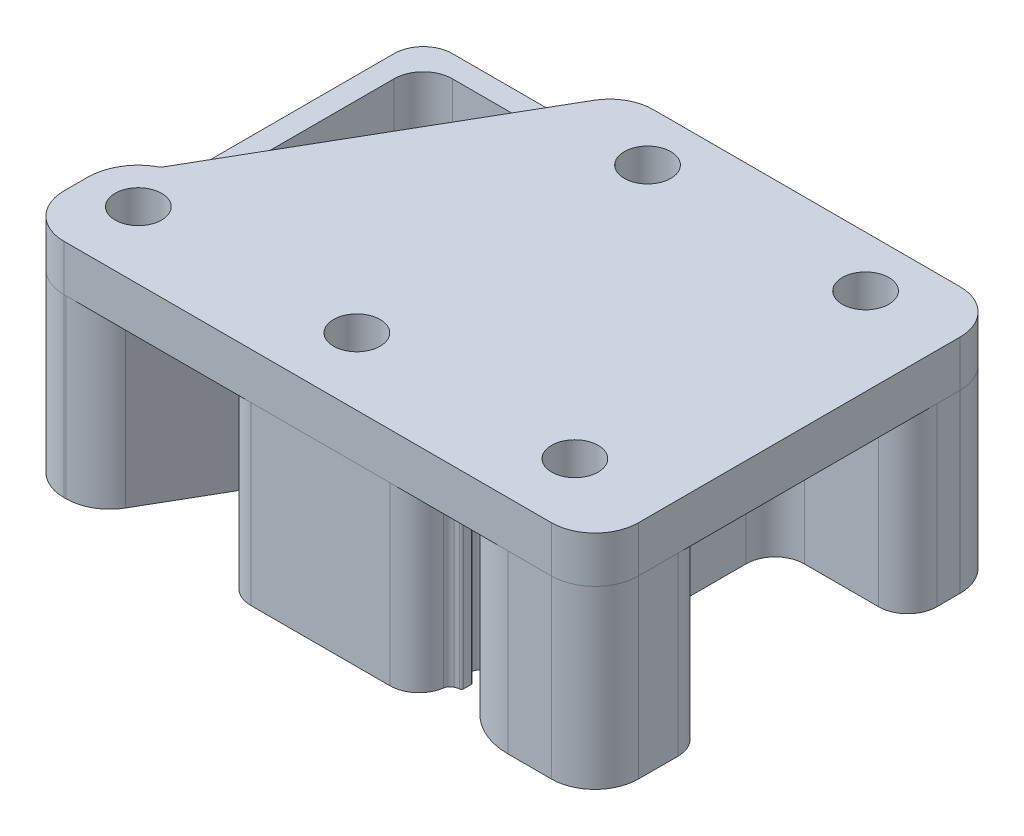
SolidWorks part; units mm, degrees
material "AISI 1045 Steel, cold drawn"
ref_plane "Front Plane" through (0, 0, 0) normal (0, 0, 1) x (1, 0, 0)
ref_plane "Top Plane" through (0, 0, 0) normal (0, 1, 0) x (1, 0, 0)
ref_plane "Right Plane" through (0, 0, 0) normal (1, 0, 0) x (0, 0, -1)
sketch "Sketch1" plane through (0, 0, 0) normal (0, 1, 0) x (1, 0, 0)
  line L0 (-13.5, -13.5) -> (-13.5, -14.619)
  line L1 (7.5, -10) -> (-7.5, -10) construction
  line L2 (7.5, -10) -> (7.5, 10) construction
  line L3 (7.5, 10) -> (-7.5, 10) construction
  line L4 (-7.5, -10) -> (-7.5, 10) construction
  line L5 (7.5, -10) -> (-7.5, 10) construction
  line L6 (7.5, 10) -> (-7.5, -10) construction
  line L7 (13.5, -13.5) -> (-13.5, -13.5) construction
  line L8 (13.5, -13.5) -> (13.5, 13.5)
  line L9 (13.5, 13.5) -> (-13.5, 13.5)
  line L10 (-13.5, -13.5) -> (-13.5, 13.5)
  line L11 (13.5, -13.5) -> (-13.5, 13.5) construction
  line L12 (13.5, 13.5) -> (-13.5, -13.5) construction
  line L13 (-13.5, -14.619) -> (13.5, -14.619)
  line L14 (13.5, -14.619) -> (13.5, -13.5)
  point P0 (0, 0)
  point P6 (0, 0)
  dimension "D1" = 15
  dimension "D2" = 27
  dimension "D3" = 1.119
  dimension "D4" = 20
extrude "Boss-Extrude1" add sketch "Sketch1" along normal mid plane 12.1
hole_wizard "M3 Clearance Hole1" positions "Sketch2" profile "Sketch3" hole size "M3" standard "ANSI Metric" end condition through all
sketch "Sketch2" plane through (0, 6.05, 0) normal (0, 1, 0) x (1, 0, 0)
  point P0 (-7.5, 10)
  point P3 (7.5, 10)
  point P6 (7.5, -10)
  point P9 (-7.5, -10)
sketch "Sketch3" plane through (-7.5, 6.05, -10) normal (1, 0, 0) x (0, 0, 1)
  line L0 (0, 0) -> (0, 12.1)
  line L1 (0, 12.1) -> (1.6, 12.1)
  line L2 (1.6, 12.1) -> (1.6, 0)
  line L5 (1.6, 0) -> (0, 0)
  line L11 (0, -6.35) -> (0, 107.95) construction
  dimension "Thru Hole Dia." = 3.2
  dimension "Thru Hole Depth" = 12.1
sketch "Sketch6" plane through (0, 6.05, 0) normal (0, 1, 0) x (1, 0, 0)
  line L0 (13.5, 13.5) -> (-13.5, 13.5) construction
  line L1 (-13.5, -14.619) -> (-28, -14.619)
  line L2 (-13.5, -14.619) -> (-13.5, 13.5)
  line L3 (-13.5, 13.5) -> (-28, 13.5)
  line L4 (-28, -14.619) -> (-28, 13.5)
  dimension "D1" = 28
extrude "Boss-Extrude3" add sketch "Sketch6" against normal up to surface (12.1 mm away) up to face at (-7.5, -6.05, -8.4)
sketch "Sketch8" plane through (0, 6.05, 0) normal (0, 1, 0) x (1, 0, 0)
  line L0 (-28, -14.619) -> (13.5, -14.619) construction
  line L2 (2.881, -10) -> (2.881, 4)
  line L3 (2.881, 4) -> (1.361, 4)
  line L4 (1.361, -14.619) -> (1.361, 4)
  line L5 (7.5, -14.619) -> (1.361, -14.619)
  arc A0 (2.881, -10) -> (7.5, -14.619) centre (7.5, -10) ccw
  dimension "D1" = 1.52
  dimension "D2" = 14
extrude "Cut-Extrude2" cut sketch "Sketch8" against normal up to surface (12.1 mm away) up to face at (-7.5, -6.05, -8.4)
sketch "Sketch9" plane through (0, 6.05, 0) normal (0, 1, 0) x (1, 0, 0)
  line L1 (2.881, 4) -> (6.306, 4)
  line L2 (2.881, 4) -> (2.881, -8)
  line L3 (2.881, -8) -> (6.306, -8)
  line L4 (6.306, 4) -> (6.306, -8)
  dimension "D1" = 3.425
  dimension "D2" = 12
extrude "Cut-Extrude3" cut sketch "Sketch9" against normal up to surface (12.1 mm away) up to face at (-7.5, -6.05, -8.4)
sketch "Sketch11" plane through (0, 6.05, 0) normal (0, 1, 0) x (1, 0, 0)
  line L1 (2.111, 0.7046) -> (2.111, 4.8734) construction
  line L4 (2.365, -998.8465) -> (2.365, 49001.1535) construction
  line L5 (2.111, 2.2598) -> (2.111, 2)
  line L6 (1.361, 3) -> (2.111, 3) construction
  line L7 (1.361, 4) -> (1.361, -14.619) construction
  line L8 (6.306, 4) -> (1.361, 4) construction
  line L9 (2.111, 2) -> (1.361, 2)
  line L10 (1.361, 2) -> (1.361, 4)
  line L11 (2.111, 4) -> (1.361, 4)
  line L12 (2.111, 3.7402) -> (2.111, 4)
  arc A2 (1.6728, 3.4989) -> (1.6728, 2.5011) centre (1.916, 3) ccw
  arc A4 (1.6728, 2.5011) -> (1.9806, 2.4085) centre (2.111, 3.4) ccw
  arc A5 (2.111, 2.2598) -> (1.9806, 2.4085) centre (1.961, 2.2598) ccw
  arc A6 (2.111, 3.7402) -> (1.9806, 3.5915) centre (1.961, 3.7402) cw
  arc A7 (1.6728, 3.4989) -> (1.9806, 3.5915) centre (2.111, 2.6) cw
  point P7 (1.361, 3)
  line M19 (1.361, -14.619) -> (1.361, 4)
  line M20 (1.361, 4) -> (6.306, 4)
  dimension "D3" = 0.555
  dimension "D4" = 1
  dimension "D5" = 1
  dimension "D6" = 0.15
  dimension "D1" = 0.254
  dimension "D2" = 0.75
  dimension "D7" = 1
extrude "Boss-Extrude4" add sketch "Sketch11" against normal up to surface (12.1 mm away) contours A2 A7 A6 L12 L10 M20 | L5 A5 A4 A2 L9 M19 region at (1.6833, 6.05, -3.7249) region at (1.6833, 6.05, -2.2751) up to face at (-7.5, -6.05, -8.4)
pattern_linear "LPattern1" count 9 spacing 2 along (0, 0, 1) of "Boss-Extrude4"
sketch "Sketch12" plane through (0, 6.05, 0) normal (0, 1, 0) x (1, 0, 0)
  circle A0 centre (2.111, 4) radius 0.5
  circle A1 centre (6.306, 4) radius 0.5
  circle A2 centre (6.306, -8) radius 0.5
  dimension "D1" = 1
extrude "Cut-Extrude5" cut sketch "Sketch12" against normal up to surface (12.1 mm away) up to face at (1.556, -6.05, 5.2005)
sketch "Sketch13" plane through (0, 6.05, 0) normal (0, 1, 0) x (1, 0, 0)
  line L3 (2.111, -14) -> (1.361, -14) construction
  line L4 (2.111, -13.7402) -> (2.111, -14) construction
  line L5 (2.111, -14) -> (1.361, -14)
  line L6 (2.111, -13.7402) -> (2.111, -14)
  line L7 (1.361, -14) -> (1.361, -13)
  arc A6 (1.6728, -12.5011) -> (1.6728, -13.4989) centre (1.916, -13) ccw construction
  arc A7 (1.6728, -13.4989) -> (1.9806, -13.5915) centre (2.111, -12.6) ccw construction
  arc A8 (2.111, -13.7402) -> (1.9806, -13.5915) centre (1.961, -13.7402) ccw construction
  arc A9 (1.361, -13) -> (1.6728, -13.4989) centre (1.916, -13) ccw
  arc A10 (1.6728, -13.4989) -> (1.9806, -13.5915) centre (2.111, -12.6) ccw
  arc A11 (2.111, -13.7402) -> (1.9806, -13.5915) centre (1.961, -13.7402) ccw
extrude "Cut-Extrude6" cut sketch "Sketch13" against normal up to surface (12.1 mm away) up to face at (1.6903, -6.05, 5.2284)
fillet "Fillet3" radius 0.5 7 edges at (5.806, 0, 8) (6.306, 0, 7.5) (5.806, 0, -4) (6.306, 0, -3.5) (2.611, 0, -4) (1.8595, 0, -3.5679) (2.881, 0, 8)
sketch "Sketch17" plane through (0, 6.05, 0) normal (0, 1, 0) x (1, 0, 0)
  line L0 (-21.1595, -14.619) -> (-15.513, -17.879)
  line L11 (-6.4019, 5.9019) -> (-3.8038, 4.4019) construction
  line L12 (-6.4019, 5.9019) -> (-2.9019, 11.9641) construction
  line L13 (-3.8038, 4.4019) -> (-0.3038, 10.4641) construction
  line L14 (-2.9019, 11.9641) -> (-0.3038, 10.4641) construction
  line L15 (-4.201, 12.7141) -> (0.9952, 9.7141) construction
  line L16 (-4.201, 12.7141) -> (-2.701, 15.3122) construction
  line L17 (0.9952, 9.7141) -> (2.4952, 12.3122) construction
  line L18 (-2.701, 15.3122) -> (2.4952, 12.3122) construction
  line L19 (-5.1029, 5.1519) -> (-0.1029, 13.8122) construction
  line L20 (-21.1595, -14.619) -> (-8.5843, 7.1619)
  line L21 (-15.513, -17.879) -> (-2.9378, 3.9019)
  line L22 (-8.5843, 7.1619) -> (-2.9378, 3.9019)
  line L23 (-22.5782, -10.8263) -> (-19.8719, -12.3888) construction
  line L24 (-22.5782, -10.8263) -> (-12.5782, 6.4942) construction
  line L25 (-19.8719, -12.3888) -> (-9.8719, 4.9317) construction
  line L26 (-12.5782, 6.4942) -> (-9.8719, 4.9317) construction
  line L27 (-28, -14.619) -> (1.361, -14.619) construction
  line L28 (-14.8719, -3.7285) -> (-17.5782, -2.166) construction
  circle A0 centre (-7.5, 10) radius 1.6 construction
  circle A1 centre (-7.5, -10) radius 1.6 construction
  dimension "D1" = 6.52
  dimension "D3" = 3
  dimension "D10" = 3
  dimension "D2" = 6
  dimension "D4" = 3
  dimension "D5" = 10
  dimension "D6" = 3.125
  dimension "D7" = 2.5
  dimension "D8" = 60
  dimension "D9" = 3
  dimension "D11" = 20
extrude "Cut-Extrude7" cut sketch "Sketch17" against normal up to surface (12.1 mm away) up to face at (1.9594, -6.05, 4.4571)
sketch "Sketch18" plane through (0, 6.05, 0) normal (0, 1, 0) x (1, 0, 0)
  line L0 (-26.0342, -14.619) -> (-26.0342, -10)
  line L2 (-14.1485, 10.3744) -> (-26.7237, -11.4065)
  line L3 (-12.344, 13.5) -> (-24.1063, -6.8729)
  line L4 (-12.344, 13.5) -> (-28, 13.5)
  line L5 (-28, 13.5) -> (-28, -14.619)
  line L7 (-28, -14.619) -> (-21.1595, -14.619) construction
  line L8 (-8.5843, 7.1619) -> (-21.1595, -14.619) construction
  line L10 (-28, -14.619) -> (-26.0342, -14.619)
  arc A2 (-24.1063, -6.8729) -> (-26.0342, -10) centre (-22.5342, -10) ccw
  point P0 (-7.5, -10)
  dimension "D2" = 3.5
  dimension "D1" = 6.425
extrude "Cut-Extrude8" cut sketch "Sketch18" against normal up to surface (12.1 mm away) contours A2 L10 | A2 L3 L4 L5 L10 region at (-22.8632, 6.05, -4.1187) up to face at (1.2277, -6.05, 4.4618)
hole_wizard "M3 Clearance Hole2" positions "Sketch19" profile "Sketch20" hole size "M3" standard "ANSI Metric" end condition up to next
sketch "Sketch19" plane through (0, 6.05, 0) normal (0, 1, 0) x (1, 0, 0)
  point P0 (-22.5342, -10)
sketch "Sketch20" plane through (-22.5342, 6.05, 10) normal (1, 0, 0) x (0, 0, 1)
  line L0 (0, 0) -> (0, 12.1)
  line L1 (0, 12.1) -> (1.6, 12.1)
  line L2 (1.6, 12.1) -> (1.6, 0)
  line L5 (1.6, 0) -> (0, 0)
  line L11 (0, -6.35) -> (0, 107.95) construction
  dimension "Thru Hole Dia." = 3.2
  dimension "Thru Hole Depth" = 12.1
fillet "Fillet4" radius 3 5 edges at (13.5, 0, 14.619) (13.5, 0, -13.5) (-12.344, 0, -13.5) (-26.0342, 0, 14.619) (-21.1595, 0, 14.619)
sketch "Sketch21" plane through (0, 6.05, 0) normal (0, 1, 0) x (1, 0, 0)
  line L0 (-8.5843, 7.1619) -> (-20.2935, -13.119) construction
  line L1 (-17.8343, -8.8595) -> (-20.8004, -7.147)
  line L2 (-17.8343, -8.8595) -> (-9.3343, 5.8629)
  line L3 (-20.8004, -7.147) -> (-12.3004, 7.5754)
  line L4 (-9.3343, 5.8629) -> (-12.3004, 7.5754)
  line L5 (-2.9378, 3.9019) -> (-8.5843, 7.1619) construction
  dimension "D3" = 17
  dimension "D1" = 3.425
  dimension "D2" = 1.5
extrude "Cut-Extrude9" cut sketch "Sketch21" against normal up to surface (12.1 mm away) up to face at (-22.5342, -6.05, 11.6)
sketch "Sketch22" plane through (0, 6.05, 0) normal (0, 1, 0) x (1, 0, 0)
  circle A0 centre (-20.8004, -7.147) radius 0.5
  circle A1 centre (-12.3004, 7.5754) radius 0.5
  circle A2 centre (-8.5843, 7.1619) radius 0.5
  circle A3 centre (-2.9378, 3.9019) radius 0.5
  arc A4 (2.544, 4.25) -> (1.6303, 3.8625) centre (2.111, 4) ccw construction
extrude "Cut-Extrude10" cut sketch "Sketch22" against normal up to surface (12.1 mm away) up to face at (-22.5342, -6.05, 11.6)
fillet "Fillet5" radius 0.5 10 edges at (-17.8343, 0, 8.8595) (-3.1878, 0, -3.4689) (-3.3708, 0, -4.1519) (-8.8343, 0, -6.7289) (-8.1513, 0, -6.9119) (-11.8674, 0, -7.3254) (-12.5504, 0, -7.1424) (-20.5504, 0, 6.714) (-20.3674, 0, 7.397) (-9.3343, 0, -5.8629)
ref_plane "Plane2" through (6.9551, 0, -12.0466) normal (0.5, 0, -0.866) x (-0.866, 0, -0.5)
sketch "Sketch29" plane through (0, 6.05, 0) normal (0, 1, 0) x (1, 0, 0)
  line L0 (-13.21, 12) -> (-24.1063, -6.8729) construction
  line L1 (-26.0342, -11.619) -> (-26.0342, -10) construction
  line L2 (13.5, -11.619) -> (13.5, 10.5) construction
  line L3 (10.5, 13.5) -> (-10.6119, 13.5) construction
  line L5 (-23.0342, -14.619) -> (10.5, -14.619)
  line L6 (-26.0342, -11.619) -> (-26.0342, -10)
  line L7 (13.5, -11.619) -> (13.5, 10.5)
  line L8 (10.5, 13.5) -> (-10.6119, 13.5)
  line L10 (-13.21, 12) -> (-24.1063, -6.8729)
  arc A0 (-24.1063, -6.8729) -> (-26.0342, -10) centre (-22.5342, -10) ccw construction
  arc A1 (-26.0342, -11.619) -> (-23.0342, -14.619) centre (-23.0342, -11.619) ccw construction
  arc A2 (10.5, -14.619) -> (13.5, -11.619) centre (10.5, -11.619) ccw construction
  arc A3 (13.5, 10.5) -> (10.5, 13.5) centre (10.5, 10.5) ccw construction
  arc A4 (-10.6119, 13.5) -> (-13.21, 12) centre (-10.6119, 10.5) ccw construction
  arc A5 (-24.1063, -6.8729) -> (-26.0342, -10) centre (-22.5342, -10) ccw
  arc A6 (-26.0342, -11.619) -> (-23.0342, -14.619) centre (-23.0342, -11.619) ccw
  arc A7 (10.5, -14.619) -> (13.5, -11.619) centre (10.5, -11.619) ccw
  arc A8 (13.5, 10.5) -> (10.5, 13.5) centre (10.5, 10.5) ccw
  arc A9 (-10.6119, 13.5) -> (-13.21, 12) centre (-10.6119, 10.5) ccw
  circle A12 centre (-22.5342, -10) radius 1.6 construction
  circle A13 centre (-7.5, -10) radius 1.6 construction
  circle A14 centre (7.5, -10) radius 1.6 construction
  circle A15 centre (7.5, 10) radius 1.6 construction
  circle A16 centre (-7.5, 10) radius 1.6 construction
  circle A17 centre (-22.5342, -10) radius 1.6
  circle A18 centre (-7.5, -10) radius 1.6
  circle A19 centre (7.5, -10) radius 1.6
  circle A20 centre (7.5, 10) radius 1.6
  circle A21 centre (-7.5, 10) radius 1.6
extrude "Boss-Extrude7" add sketch "Sketch29" along normal blind 3.175 separate body
hole_wizard "CBORE for M3 SHCS1" positions "Sketch23" profile "Sketch25" counterbore size "M3" standard "ANSI Metric" end condition up to next
sketch "Sketch23" plane through (6.9551, 0, -12.0466) normal (0.5, 0, -0.866) x (-0.866, 0, -0.5)
  line L0 (4.4952, -6.05) -> (9.4952, 6.05) construction
  line L1 (-2.3433, -6.05) -> (15.9402, -6.05) construction
  line L3 (-2.3433, 6.05) -> (15.9402, 6.05) construction
  point P15 (6.9952, 0)
  dimension "D1" = 5
sketch "Sketch25" plane through (0.8971, 0, -15.5442) normal (0, 1, 0) x (-0.866, 0, -0.5)
  line L0 (0, 0) -> (0, 12)
  line L1 (0, 12) -> (1.6, 12)
  line L3 (1.6, 12) -> (1.6, 6)
  line L4 (1.6, 6) -> (3.25, 6)
  line L5 (3.25, 6) -> (3.25, 0)
  line L7 (3.25, 0) -> (0, 0)
  line L11 (0, -6.35) -> (0, 107.95) construction
  dimension "Thru Hole Dia." = 3.2
  dimension "Thru Hole Depth" = 12
  dimension "C'Bore Dia." = 6.5
  dimension "C'Bore Depth" = 6
sketch "Sketch30" plane through (0, 6.05, 0) normal (0, 1, 0) x (1, 0, 0)
  line L1 (3.381, -8) -> (5.44, -8) construction
  line L2 (6.306, -7.134) -> (6.306, 3.134) construction
  line L3 (5.44, 4) -> (2.977, 4) construction
  line L4 (3.381, -8) -> (5.44, -8)
  line L5 (6.306, -7.134) -> (6.306, 3.134)
  line L6 (5.44, 4) -> (2.977, 4)
  line L7 (-18.0843, -9.2926) -> (-9.0843, 6.2959)
  line L8 (-20.0504, -7.5801) -> (-18.2673, -8.6095) construction
  line L9 (-12.7335, 6.8254) -> (-20.3674, -6.397) construction
  line L10 (-9.7673, 6.1129) -> (-11.5504, 7.1424) construction
  line L11 (-20.0504, -7.5801) -> (-18.2673, -8.6095)
  line L12 (-12.7335, 6.8254) -> (-20.3674, -6.397)
  line L13 (-9.7673, 6.1129) -> (-11.5504, 7.1424)
  line L14 (2.881, -8.5) -> (2.881, 4.0093)
  arc A0 (3.381, -8) -> (2.881, -8.5) centre (3.381, -8.5) ccw construction
  arc A1 (5.873, -8.25) -> (5.44, -8) centre (5.44, -8.5) ccw construction
  arc A2 (5.873, -8.25) -> (6.556, -7.567) centre (6.306, -8) ccw construction
  arc A3 (6.306, -7.134) -> (6.556, -7.567) centre (6.806, -7.134) ccw construction
  arc A4 (6.556, 3.567) -> (6.306, 3.134) centre (6.806, 3.134) ccw construction
  arc A5 (6.556, 3.567) -> (5.873, 4.25) centre (6.306, 4) ccw construction
  arc A6 (5.44, 4) -> (5.873, 4.25) centre (5.44, 4.5) ccw construction
  arc A7 (2.544, 4.25) -> (2.977, 4) centre (2.977, 4.5) ccw construction
  arc A8 (3.381, -8) -> (2.881, -8.5) centre (3.381, -8.5) ccw
  arc A9 (5.873, -8.25) -> (5.44, -8) centre (5.44, -8.5) ccw
  arc A10 (5.873, -8.25) -> (6.556, -7.567) centre (6.306, -8) ccw
  arc A11 (6.306, -7.134) -> (6.556, -7.567) centre (6.806, -7.134) ccw
  arc A12 (6.556, 3.567) -> (6.306, 3.134) centre (6.806, 3.134) ccw
  arc A13 (6.556, 3.567) -> (5.873, 4.25) centre (6.306, 4) ccw
  arc A14 (5.44, 4) -> (5.873, 4.25) centre (5.44, 4.5) ccw
  arc A15 (2.881, 4.0093) -> (2.977, 4) centre (2.977, 4.5) ccw
  arc A17 (-18.0843, -9.2926) -> (-18.2673, -8.6095) centre (-18.5173, -9.0426) ccw construction
  arc A18 (-20.0504, -7.5801) -> (-20.5504, -7.5801) centre (-20.3004, -8.0131) ccw construction
  arc A19 (-20.8004, -6.647) -> (-20.3674, -6.397) centre (-20.8004, -6.147) ccw construction
  arc A20 (-12.7335, 6.8254) -> (-12.7335, 7.3254) centre (-13.1665, 7.0754) ccw construction
  arc A21 (-11.8004, 7.5754) -> (-12.7335, 7.3254) centre (-12.3004, 7.5754) ccw construction
  arc A22 (-11.8004, 7.5754) -> (-11.5504, 7.1424) centre (-11.3004, 7.5754) ccw construction
  arc A23 (-9.7673, 6.1129) -> (-9.0843, 6.2959) centre (-9.5173, 6.5459) ccw construction
  arc A24 (-18.0843, -9.2926) -> (-18.2673, -8.6095) centre (-18.5173, -9.0426) ccw
  arc A25 (-20.0504, -7.5801) -> (-20.5504, -7.5801) centre (-20.3004, -8.0131) ccw
  arc A26 (-20.8004, -6.647) -> (-20.3674, -6.397) centre (-20.8004, -6.147) ccw
  arc A27 (-12.7335, 6.8254) -> (-12.7335, 7.3254) centre (-13.1665, 7.0754) ccw
  arc A28 (-11.8004, 7.5754) -> (-12.7335, 7.3254) centre (-12.3004, 7.5754) ccw
  arc A29 (-11.8004, 7.5754) -> (-11.5504, 7.1424) centre (-11.3004, 7.5754) ccw
  arc A30 (-9.7673, 6.1129) -> (-9.0843, 6.2959) centre (-9.5173, 6.5459) ccw
  arc A31 (-20.8004, -6.647) -> (-20.5504, -7.5801) centre (-20.8004, -7.147) ccw construction
  arc A32 (-20.8004, -6.647) -> (-20.5504, -7.5801) centre (-20.8004, -7.147) ccw
  point P2 (2.881, 6.0093)
  point P29 (0, 0)
extrude "Boss-Extrude8" add sketch "Sketch30" against normal up to surface (12.1 mm away) up to face at (-22.5342, -6.05, 11.6)
fillet "Fillet6" radius 1 1 edges at (2.881, 0, -4.0093)
sketch "Sketch31" plane through (0, 6.05, 0) normal (0, 1, 0) x (1, 0, 0)
  line L0 (13.5, 6.9) -> (4.381, 6.9)
  line L2 (4.381, 6.9) -> (4.381, -6.9)
  line L3 (4.381, -6.9) -> (13.5, -6.9)
  line L4 (2.881, -10) -> (2.881, 3.4759) construction
  line L6 (13.5, 6.9) -> (13.5, -6.9)
  line L7 (13.5, -11.619) -> (13.5, 10.5) construction
  circle A0 centre (7.5, -10) radius 1.6 construction
  circle A1 centre (7.5, 10) radius 1.6 construction
  point P0 (13.5, -6.4)
  dimension "D1" = 3.1
  dimension "D2" = 3.1
  dimension "D3" = 1.5
extrude "Cut-Extrude11" cut sketch "Sketch31" against normal up to surface (12.1 mm away) up to face at (-0.8329, -6.05, 3.7569)
sketch "Sketch32" plane through (0, 6.05, 0) normal (0, 1, 0) x (1, 0, 0)
  line L0 (-10.0574, 7.6105) -> (-19.366, -8.5125)
  line L1 (-9.0173, 6.4119) -> (-20.2935, -13.119) construction
  line L2 (-13.21, 12) -> (-24.1063, -6.8729) construction
  line L3 (-13.21, 12) -> (-24.1063, -6.8729)
  line L5 (10.5, 13.5) -> (-10.6119, 13.5) construction
  line L6 (-7.5, 13.5) -> (-10.6119, 13.5)
  arc A0 (-19.366, -8.5125) -> (-24.1063, -6.8729) centre (-22.5342, -10) ccw
  arc A1 (-24.1063, -6.8729) -> (-26.0342, -10) centre (-22.5342, -10) ccw construction
  arc A2 (-7.5, 13.5) -> (-10.0574, 7.6105) centre (-7.5, 10) ccw
  arc A3 (-10.6119, 13.5) -> (-13.21, 12) centre (-10.6119, 10.5) ccw construction
  arc A4 (-10.6119, 13.5) -> (-13.21, 12) centre (-10.6119, 10.5) ccw
  point P16 (-10.3897, 8.0252)
  dimension "D1" = 1.5
extrude "Cut-Extrude12" cut sketch "Sketch32" against normal up to surface (12.1 mm away) up to face at (-0.3561, -6.05, 3.5736)
sketch "Sketch34" plane through (0, -6.05, 0) normal (0, -1, 0) x (1, 0, 0)
  line L0 (0.111, -6.1826) -> (-7.4426, 6.9005)
  line L1 (-3.3708, -3.1519) -> (-13.6309, 14.619) construction
  line L2 (0.111, -6.1826) -> (0.111, 12.619)
  line L4 (0.111, 12.619) -> (-5.8414, 12.619)
  line L5 (2.111, 10.2598) -> (2.111, 9.7402) construction
  line L7 (-13.6309, 14.619) -> (1.361, 14.619) construction
  circle A2 centre (-7.5, 10) radius 3.1
  arc A3 (-7.4426, 6.9005) -> (-5.8414, 12.619) centre (-7.5, 10) ccw
  dimension "D2" = 1.5
  dimension "D3" = 2
  dimension "D4" = 2
  dimension "D1" = 1.5
extrude "Cut-Extrude14" cut sketch "Sketch34" against normal up to surface (12.1 mm away) up to face at (-0.2449, 6.05, 3.6119)
sketch "Sketch35" plane through (0, -6.05, 0) normal (0, -1, 0) x (1, 0, 0)
  line L0 (-4.9175, -11.9731) -> (0.7117, -8.7231) construction
  line L1 (-7.5622, -13.5) -> (1.2713, -8.4)
  line L2 (10.5, -13.5) -> (-7.5, -13.5) construction
  line L3 (1.2713, -8.4) -> (4.3871, -8.4)
  line L4 (7.5, -13.5) -> (-7.5622, -13.5)
  line L6 (4.381, -6.9) -> (13.5, -6.9) construction
  circle A1 centre (7.5, -10) radius 1.6 construction
  arc A3 (4.3871, -8.4) -> (7.5, -13.5) centre (7.5, -10) ccw
  point P2 (1.5688, -8.2282)
  point P10 (7.5305, -13.5)
  point P13 (4.1171, -8.9064)
  point P14 (0, 0)
  dimension "D1" = 1.5
extrude "Cut-Extrude15" cut sketch "Sketch35" against normal up to surface (12.1 mm away) up to face at (-2.7337, 6.05, 6.3401)
fillet "Fillet7" radius 2 9 edges at (-13.6309, 0, 14.619) (1.361, 0, 14.619) (13.5, 0, 6.9) (4.381, 0, 6.9) (13.5, 0, -6.9) (4.381, 0, -6.9) (-19.366, 0, 8.5125) (-7.5612, 0, -13.4995) (-10.0574, 0, -7.6105)
fillet "Fillet8" radius 1 6 edges at (0.111, 0, 12.619) (0.111, 0, -6.1826) (-5.8414, 0, 12.619) (-7.4426, 0, 6.9005) (4.3871, 0, -8.4) (1.2713, 0, -8.4)
sketch "Sketch36" plane through (0, 6.05, 0) normal (0, 1, 0) x (1, 0, 0)
  line L0 (2.881, 4.4759) -> (2.881, 3.4759)
  line L1 (1.611, 4) -> (1.611, 4.4759)
  arc A0 (1.611, 4.4759) -> (2.881, 4.4759) centre (2.246, 4.4759) cw
  arc A3 (2.544, 4.25) -> (1.6303, 3.8625) centre (2.111, 4) ccw construction
  arc A4 (2.544, 4.25) -> (2.6117, 4.1586) centre (2.977, 4.5) ccw construction
  arc A5 (2.881, 3.4759) -> (2.6117, 4.1586) centre (1.881, 3.4759) ccw construction
  arc A6 (2.544, 4.25) -> (1.611, 4) centre (2.111, 4) ccw
  arc A7 (2.544, 4.25) -> (2.6117, 4.1586) centre (2.977, 4.5) ccw
  arc A8 (2.881, 3.4759) -> (2.6117, 4.1586) centre (1.881, 3.4759) ccw
  point P9 (1.611, 4)
  dimension "D1" = 1
extrude "Cut-Extrude16" cut sketch "Sketch36" against normal up to surface (12.1 mm away) up to face at (-2.9137, -6.05, 6.8822)
sketch "Sketch37" plane through (0, 6.05, 0) normal (0, 1, 0) x (1, 0, 0)
  line L0 (-10.6817, 6.5291) -> (-9.847, 7.9748)
  line L1 (-18.0522, -6.2369) -> (-10.6817, 6.5291) construction
  line L2 (1.0392, 8.534) -> (-6.9682, 13.1571) construction
  line L3 (-6.6764, 12.9886) -> (-6.9682, 13.1571)
  arc A0 (-6.6764, 12.9886) -> (-9.847, 7.9748) centre (-7.5, 10) ccw
  circle A1 centre (-7.5, 10) radius 1.6 construction
  arc A2 (-6.9682, 13.1571) -> (-8.5926, 13.3251) centre (-7.9682, 11.425) ccw construction
  arc A3 (-8.5926, 13.3251) -> (-10.6269, 8.4276) centre (-7.5, 10) ccw construction
  arc A4 (-10.6817, 6.5291) -> (-10.6269, 8.4276) centre (-12.4137, 7.5291) ccw construction
  arc A5 (-6.9682, 13.1571) -> (-8.5926, 13.3251) centre (-7.9682, 11.425) ccw
  arc A6 (-8.5926, 13.3251) -> (-10.6269, 8.4276) centre (-7.5, 10) ccw
  arc A7 (-10.6817, 6.5291) -> (-10.6269, 8.4276) centre (-12.4137, 7.5291) ccw
  dimension "D1" = 1.5
extrude "Cut-Extrude17" cut sketch "Sketch37" against normal up to surface (12.1 mm away) up to face at (-2.9137, -6.05, 6.8822)
fillet "Fillet9" radius 2 2 edges at (-6.6764, 0, -12.9886) (-9.847, 0, -7.9748)
sketch "Sketch38" plane through (0, 6.05, 0) normal (0, 1, 0) x (1, 0, 0)
  line L0 (-26.0342, -10) -> (-26.0342, 13.1)
  line L1 (-26.0342, 13.1) -> (-7.5, 13.1)
  line L2 (-24.5342, -7.1277) -> (-24.5342, 11.6)
  line L3 (-24.5342, 11.6) -> (-10.1552, 11.6)
  line L4 (-24.5342, -10) -> (-24.5342, 11.6) construction
  line L5 (-24.5342, 11.6) -> (-7.5, 11.6) construction
  arc A0 (-7.2093, 13.0863) -> (-10.3388, 8.7545) centre (-7.5, 10) ccw construction
  arc A1 (-7.5, 13.1) -> (-10.1552, 11.6) centre (-7.5, 10) ccw
  arc A2 (-20.7842, -6.9689) -> (-26.0342, -10) centre (-22.5342, -10) ccw construction
  arc A3 (-24.5342, -7.1277) -> (-26.0342, -10) centre (-22.5342, -10) ccw
  point P3 (-26.0342, 12.3382)
  dimension "D1" = 1.5
extrude "Boss-Extrude9" add sketch "Sketch38" against normal up to surface (12.1 mm away) up to face at (-2.9137, -6.05, 6.8822)
fillet "Fillet10" radius 2 4 edges at (-24.5342, 0, 7.1277) (-10.1552, 0, -11.6) (-26.0342, 0, -13.1) (-24.5342, 0, -11.6)
